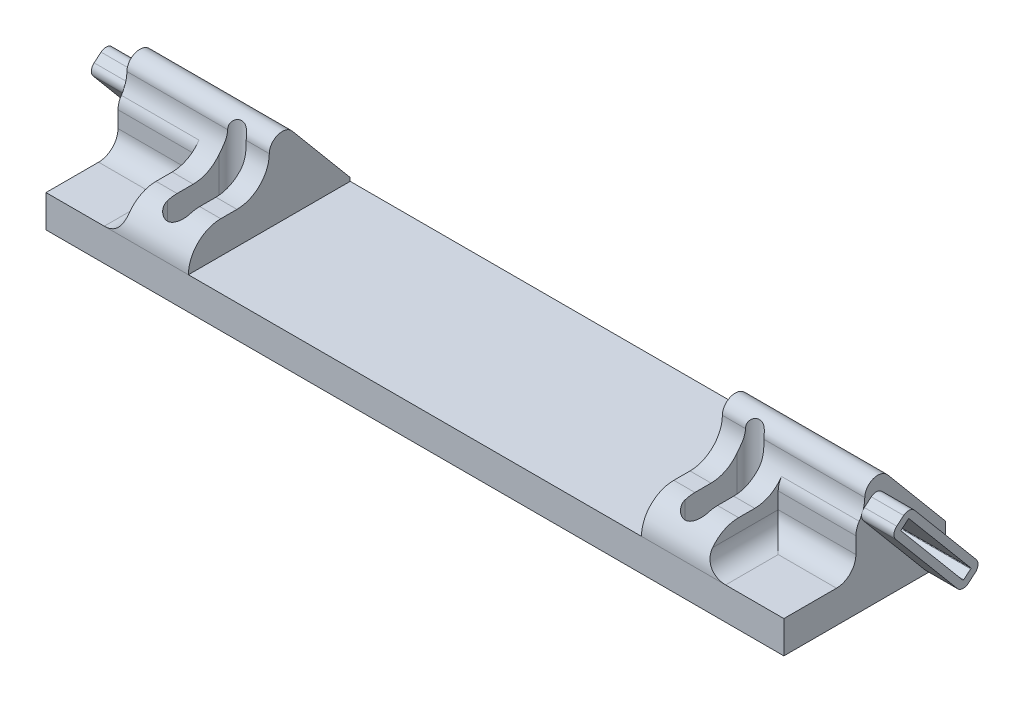
SolidWorks part; units mm, degrees
ref_plane "Front Plane" through (0, 0, 0) normal (0, 0, 1) x (1, 0, 0)
ref_plane "Top Plane" through (0, 0, 0) normal (0, 1, 0) x (1, 0, 0)
ref_plane "Right Plane" through (0, 0, 0) normal (1, 0, 0) x (0, 0, -1)
sketch "Sketch1" plane through (0, 0, 0) normal (0, 1, 0) x (1, 0, 0)
  line L1 (-57, -12.5) -> (57, -12.5)
  line L2 (-57, -12.5) -> (-57, 12.5)
  line L3 (-57, 12.5) -> (57, 12.5)
  line L4 (57, -12.5) -> (57, 12.5)
  line L5 (-57, -12.5) -> (57, 12.5) construction
  line L6 (-57, 12.5) -> (57, -12.5) construction
  point P0 (0, 0)
  dimension "D1" = 114
  dimension "D2" = 25
extrude "Boss-Extrude1" add sketch "Sketch1" along normal blind 20
sketch "Sketch3" plane through (57, 0, 0) normal (1, 0, 0) x (0, 0, -1)
  line L1 (11.4337, 2.2689) -> (1.7919, 13.7596)
  line L2 (11.4337, 2.2689) -> (10.2081, 1.2404)
  line L3 (1.7919, 13.7596) -> (0.5663, 12.7311)
  line L4 (10.2081, 1.2404) -> (0.5663, 12.7311)
  line L5 (11.4337, 2.2689) -> (0.5663, 12.7311) construction
  line L6 (1.7919, 13.7596) -> (10.2081, 1.2404) construction
  line L7 (13.75, 0) -> (-13.75, 0) construction
  line L8 (12.5, 20) -> (12.5, 0) construction
  point P0 (1.1791, 13.2453)
  point P1 (6, 7.5)
  point P2 (10.8209, 1.7547)
  dimension "D1" = 15
  dimension "D2" = 1.6
  dimension "D3" = 50
  dimension "D4" = 7.5
  dimension "D6" = 6.5
extrude "Cut-Extrude1" cut sketch "Sketch3" against normal blind 10
mirror "Mirror1" about plane through (0, 0, 0) normal (1, 0, 0) of "Cut-Extrude1"
sketch "Sketch4" plane through (0, 20, 0) normal (0, 1, 0) x (1, 0, 0)
  line L0 (57, -12.5) -> (57, 12.5) construction
  line L1 (-57, -12.5) -> (57, -12.5)
  line L2 (-57, -12.5) -> (-57, 0)
  line L3 (-57, 0) -> (57, 0)
  line L4 (57, -12.5) -> (57, 0)
extrude "Cut-Extrude2" cut sketch "Sketch4" against normal blind 10
fillet "Fillet1" radius 5 2 edges at (0, 10, 12.5) (0, 10, 0)
fillet "Fillet2" radius 5 1 edges at (0, 20, 0)
fillet "Fillet4" radius 0.1 4 edges at (-52, 13.7596, -1.7919) (-52, 12.7311, -0.5663) (-52, 1.2404, -10.2081) (-52, 2.2689, -11.4337)
fillet "Fillet5" radius 0.1 20 edges at (-57, 1.7547, -10.8209) (-57, 6.9858, -5.3872) (-57, 13.2453, -1.1791) (-57, 8.0142, -6.6128) (-47, 8.0142, -6.6128) (-47, 13.2453, -1.1791) (-47, 6.9858, -5.3872) (-47, 1.7547, -10.8209) (-57, 13.7183, -1.7883) (-47, 13.7183, -1.7883) (-57, 12.7275, -0.6075) (-47, 12.7275, -0.6075) (-57, 1.2817, -10.2117) (-47, 1.2817, -10.2117) (-57, 2.2725, -11.3925) (-47, 2.2725, -11.3925) (52, 1.2404, -10.2081) (52, 2.2689, -11.4337) (52, 13.7596, -1.7919) (52, 12.7311, -0.5663)
sketch "Sketch5" plane through (0, 0, 0) normal (0, -1, 0) x (1, 0, 0)
  line L0 (-40, 1) -> (-40, 9) construction
  line L1 (-40, 5) -> (40, 5) construction
  line L2 (-41.75, 1) -> (-41.75, 9)
  line L3 (-38.25, 1) -> (-38.25, 9)
  line L4 (11, 0) -> (-11, 0) construction
  line L5 (40, 1) -> (40, 9) construction
  line L6 (38.25, 1) -> (38.25, 9)
  line L7 (41.75, 1) -> (41.75, 9)
  line L8 (0, -11) -> (0, 11) construction
  arc A0 (-41.75, 1) -> (-38.25, 1) centre (-40, 1) ccw
  arc A1 (-38.25, 9) -> (-41.75, 9) centre (-40, 9) ccw
  arc A2 (38.25, 1) -> (41.75, 1) centre (40, 1) ccw
  arc A3 (41.75, 9) -> (38.25, 9) centre (40, 9) ccw
  point P4 (-40, 5)
  point P11 (40, 5)
  dimension "D1" = 3.5
  dimension "D2" = 8
  dimension "D3" = 5
  dimension "D4" = 3.5
  dimension "D5" = 8
  dimension "D6" = 80
  dimension "D7" = 40
extrude "Cut-Extrude3" cut sketch "Sketch5" against normal blind 20
sketch "Sketch6" plane through (0, 0, -12.5) normal (0, 0, -1) x (-1, 0, 0)
  line L0 (-35, 5) -> (35, 5)
  line L1 (-35, 5) -> (-35, 20)
  line L2 (35, 5) -> (35, 20)
  line L3 (-35, 20) -> (35, 20)
  line L4 (0, 11) -> (0, -11) construction
  line L5 (-57, 20) -> (57, 20) construction
  dimension "D1" = 70
  dimension "D2" = 35
  dimension "D3" = 15
extrude "Cut-Extrude4" cut sketch "Sketch6" against normal through all
sketch "Sketch10" plane through (57, 0, 0) normal (1, 0, 0) x (0, 0, -1)
  line L0 (0.6305, 12.6545) -> (10.1438, 1.317) construction
  line L1 (11.3695, 2.3455) -> (1.8562, 13.683) construction
  line L2 (1.7153, 13.6953) -> (0.6429, 12.7954) construction
  line L3 (10.2847, 1.3047) -> (11.3571, 2.2046) construction
  line L4 (0.6305, 12.6545) -> (10.1438, 1.317)
  line L5 (11.3695, 2.3455) -> (1.8562, 13.683)
  line L6 (1.7153, 13.6953) -> (0.6429, 12.7954)
  line L7 (10.2847, 1.3047) -> (11.3571, 2.2046)
  line L8 (-0.2121, 11.9474) -> (9.3011, 0.61)
  line L9 (10.9917, 0.4621) -> (12.0642, 1.362)
  line L10 (12.2121, 3.0526) -> (2.6989, 14.39)
  line L11 (1.0083, 14.5379) -> (-0.0642, 13.638)
  arc A0 (0.6429, 12.7954) -> (0.6305, 12.6545) centre (0.7071, 12.7188) ccw construction
  arc A1 (1.8562, 13.683) -> (1.7153, 13.6953) centre (1.7796, 13.6187) ccw construction
  arc A2 (10.1438, 1.317) -> (10.2847, 1.3047) centre (10.2204, 1.3813) ccw construction
  arc A3 (11.3571, 2.2046) -> (11.3695, 2.3455) centre (11.2929, 2.2812) ccw construction
  arc A4 (0.6429, 12.7954) -> (0.6305, 12.6545) centre (0.7071, 12.7188) ccw
  arc A5 (1.8562, 13.683) -> (1.7153, 13.6953) centre (1.7796, 13.6187) ccw
  arc A6 (10.1438, 1.317) -> (10.2847, 1.3047) centre (10.2204, 1.3813) ccw
  arc A7 (11.3571, 2.2046) -> (11.3695, 2.3455) centre (11.2929, 2.2812) ccw
  arc A8 (9.3011, 0.61) -> (10.9917, 0.4621) centre (10.2204, 1.3813) ccw
  arc A9 (12.0642, 1.362) -> (12.2121, 3.0526) centre (11.2929, 2.2812) ccw
  arc A10 (2.6989, 14.39) -> (1.0083, 14.5379) centre (1.7796, 13.6187) ccw
  arc A11 (-0.0642, 13.638) -> (-0.2121, 11.9474) centre (0.7071, 12.7188) ccw
  dimension "D1" = 1.1
extrude "Boss-Extrude2" add sketch "Sketch10" along normal blind 5
mirror "Mirror2" about plane through (0, 0, 0) normal (1, 0, 0) of "Boss-Extrude2"
sketch "Sketch11" plane through (57, 0, 0) normal (1, 0, 0) x (0, 0, -1)
  line L0 (12.5, 5.5242) -> (-0.3719, 20.8644)
  line L1 (12.5, 20) -> (12.5, 0) construction
  line L2 (-0.3719, 20.8644) -> (15.8565, 20.4026)
  line L3 (15.8565, 20.4026) -> (12.5, 5.5242)
  line L4 (12.2121, 3.0526) -> (2.6989, 14.39) construction
extrude "Cut-Extrude5" cut sketch "Sketch11" against normal through all and the other way through all
fillet "Fillet7" radius 2 2 edges at (46, 18.5989, -1.529) (-46, 18.5989, -1.529)
sketch "Sketch12" plane through (57, 0, 0) normal (1, 0, 0) x (0, 0, -1)
  line L1 (-12.5, 5) -> (-1.3746, 5)
  line L2 (-12.5, 5) -> (-12.5, 11.5567)
  line L3 (-12.5, 11.5567) -> (-1.3746, 11.5567)
  line L4 (-1.3746, 5) -> (-1.3746, 11.5567)
  arc A0 (-5, 10) -> (-0.4856, 12.8505) centre (-5, 15) ccw construction
extrude "Cut-Extrude6" cut sketch "Sketch12" against normal blind 12
mirror "Mirror3" about plane through (0, 0, 0) normal (1, 0, 0) of "Cut-Extrude6"
fillet "Fillet8" radius 3 3 edges at (45, 5, 6.9373) (51, 5, 1.3746) (51, 11.5567, 1.3746)
fillet "Fillet9" radius 3 3 edges at (-45, 5, 6.9373) (-51, 11.5567, 1.3746) (-51, 5, 1.3746)
